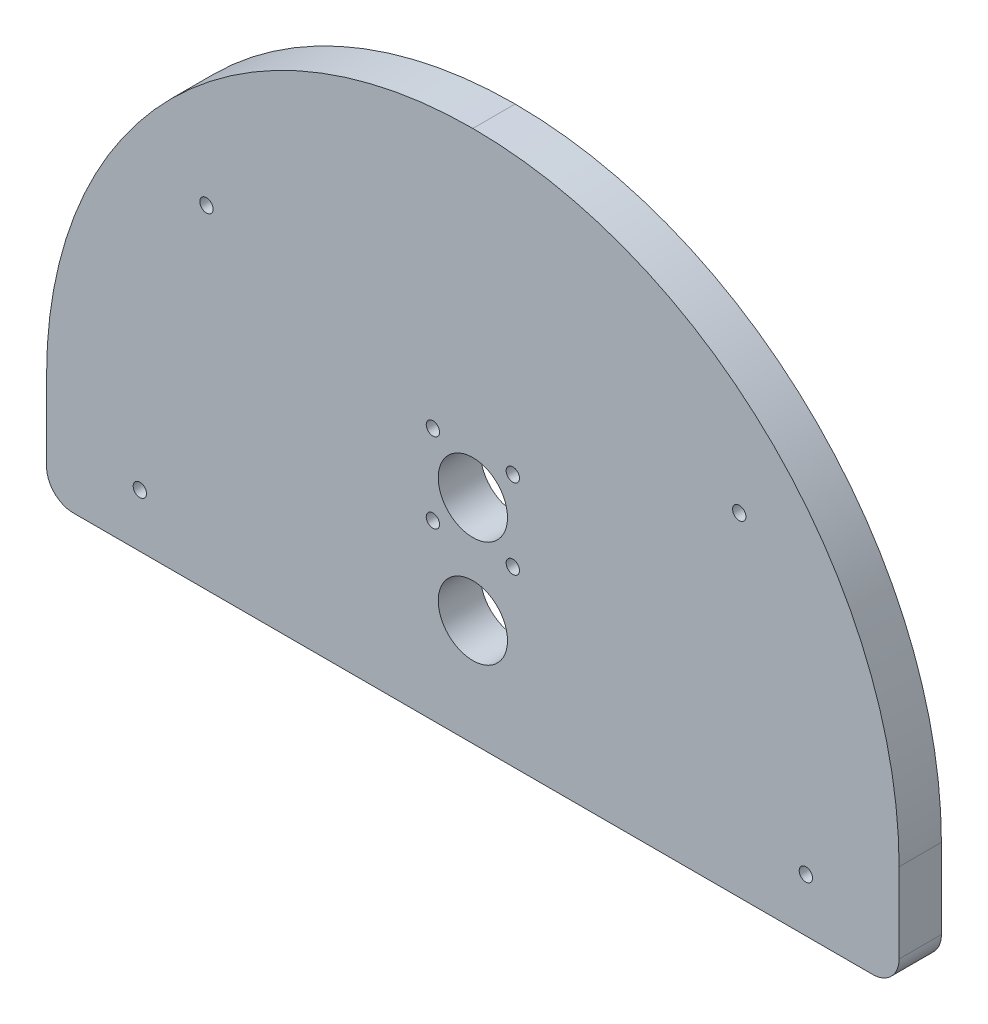
SolidWorks part; units mm, degrees
ref_plane "Front Plane" through (0, 0, 0) normal (0, 0, 1) x (1, 0, 0)
ref_plane "Top Plane" through (0, 0, 0) normal (0, 1, 0) x (1, 0, 0)
ref_plane "Right Plane" through (0, 0, 0) normal (1, 0, 0) x (0, 0, -1)
sketch "Sketch1" plane through (0, 0, 0) normal (0, 0, 1) x (1, 0, 0)
  line L1 (-160, 100) -> (160, 100)
  line L2 (-160, 100) -> (-160, -100)
  line L3 (-160, -100) -> (160, -100)
  line L4 (160, 100) -> (160, -100)
  line L5 (-160, 100) -> (160, -100) construction
  line L6 (-160, -100) -> (160, 100) construction
  point P0 (0, 0)
  dimension "D1" = 320
  dimension "D2" = 200
extrude "Boss-Extrude1" add sketch "Sketch1" along normal blind 15.875
fillet "Fillet1" radius 160 2 edges at (-160, 100, 7.9375) (160, 100, 7.9375)
fillet "Fillet2" radius 10 2 edges at (-160, -100, 7.9375) (160, -100, 7.9375)
sketch "Sketch2" plane through (0, 0, 15.875) normal (0, 0, 1) x (1, 0, 0)
  line L0 (-150, -100) -> (150, -100) construction
  circle A0 centre (0, -60) radius 13
  circle A1 centre (0, -20) radius 13
  dimension "D2" = 40
  dimension "D3" = 26
  dimension "D1" = 40
extrude "Cut-Extrude1" cut sketch "Sketch2" against normal through all
sketch "Sketch3" plane through (0, 0, 15.875) normal (0, 0, 1) x (1, 0, 0)
  line L1 (-15, -35) -> (15, -35) construction
  line L2 (-15, -35) -> (-15, -5) construction
  line L3 (-15, -5) -> (15, -5) construction
  line L4 (15, -35) -> (15, -5) construction
  line L5 (-15, -35) -> (15, -5) construction
  line L6 (-15, -5) -> (15, -35) construction
  circle A0 centre (-15, -5) radius 2.5
  circle A1 centre (-15, -35) radius 2.5
  circle A2 centre (15, -35) radius 2.5
  circle A3 centre (15, -5) radius 2.5
  point P0 (0, -20)
  dimension "D2" = 5
  dimension "D1" = 30
extrude "Cut-Extrude2" cut sketch "Sketch3" against normal through all
sketch "Sketch4" plane through (0, 0, 15.875) normal (0, 0, 1) x (1, 0, 0)
  line L0 (-125, -80) -> (125, -80) construction
  line L1 (100, 25) -> (-100, 25) construction
  line L2 (0, 25) -> (0, -80) construction
  line L3 (-150, -100) -> (150, -100) construction
  circle A0 centre (-100, 25) radius 2.5
  circle A1 centre (100, 25) radius 2.5
  circle A2 centre (125, -80) radius 2.5
  circle A3 centre (-125, -80) radius 2.5
  dimension "D5" = 5
  dimension "D1" = 20
  dimension "D2" = 125
  dimension "D3" = 200
  dimension "D4" = 250
extrude "Cut-Extrude3" cut sketch "Sketch4" against normal through all
